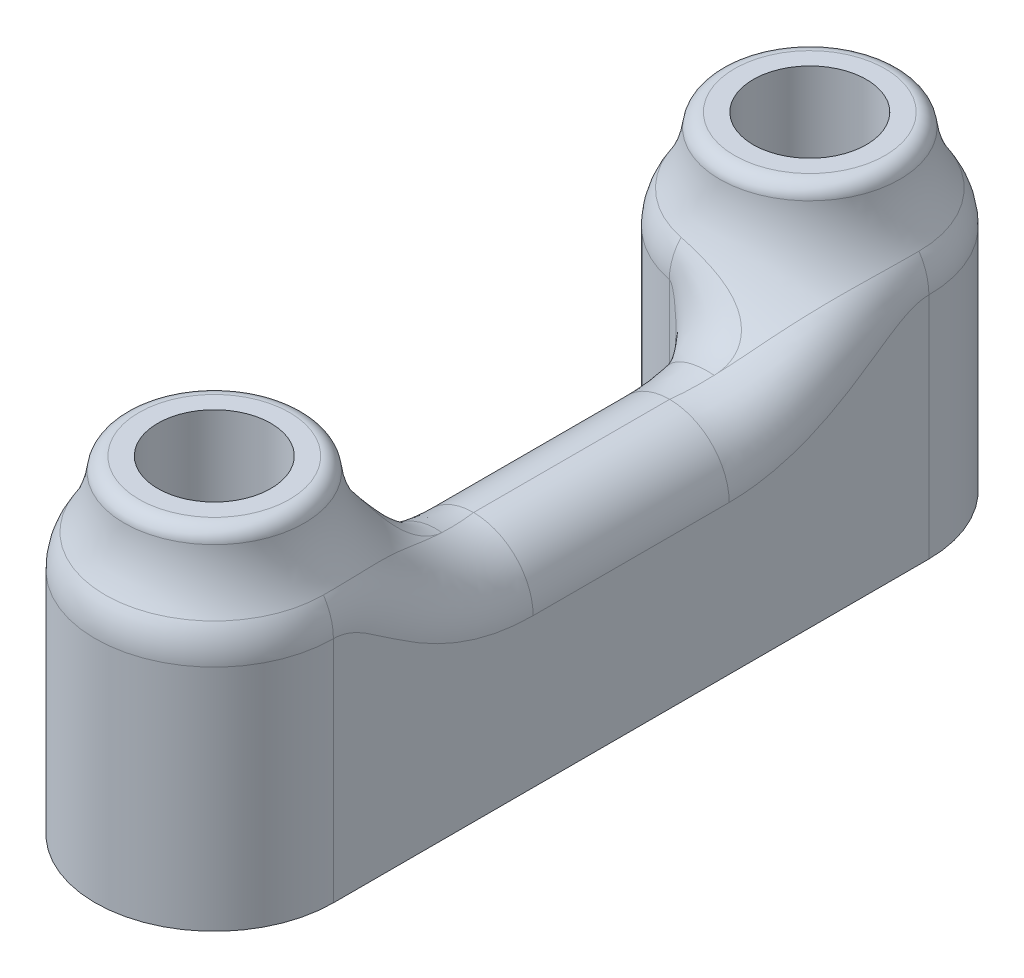
SolidWorks part; units mm, degrees
ref_plane "Front Plane" through (0, 0, 0) normal (0, 0, 1) x (1, 0, 0)
ref_plane "Top Plane" through (0, 0, 0) normal (0, 1, 0) x (1, 0, 0)
ref_plane "Right Plane" through (0, 0, 0) normal (1, 0, 0) x (0, 0, -1)
sketch "Sketch1" plane through (0, 0, 0) normal (0, 1, 0) x (1, 0, 0)
  line L0 (0, 7.62) -> (0, -7.62)
  line L1 (5.08, 12.7) -> (5.08, -12.7)
  line L2 (5.08, 0) -> (0, 0) construction
  arc A0 (5.08, 12.7) -> (0, 7.62) centre (0, 12.7) ccw
  circle A1 centre (0, 12.7) radius 2.413
  circle A2 centre (0, -12.7) radius 2.413
  arc A3 (5.08, -12.7) -> (0, -7.62) centre (0, -12.7) cw
  dimension "D1" = 4.826
  dimension "D2" = 10.16
  dimension "D3" = 12.7
extrude "Boss-Extrude1" add sketch "Sketch1" along normal blind 8.89
sketch "Sketch2" plane through (0, 8.89, 0) normal (0, 1, 0) x (1, 0, 0)
  line L0 (0, 0) -> (5.08, 0) construction
  line L1 (0, 7.62) -> (0, -7.62) construction
  line L2 (5.08, -12.7) -> (5.08, 12.7) construction
  circle A0 centre (0, 12.7) radius 2.413
  circle A1 centre (0, 12.7) radius 3.81
  circle A2 centre (0, 12.7) radius 2.413 construction
  circle A3 centre (0, -12.7) radius 3.81
  circle A4 centre (0, -12.7) radius 2.413
  dimension "D1" = 7.62
extrude "Boss-Extrude2" add sketch "Sketch2" along normal blind 5.08
fillet "Fillet1" radius 5.08 2 edges at (0, 8.89, 8.89) (0, 8.89, -8.89)
fillet "Fillet2" radius 1.27 2 edges at (0, 5.3049, -7.62) (0, 5.3049, 7.62)
fillet "Fillet3" radius 2.54 10 edges at (0, 9.083, -5.1968) (-0.494, 10.4371, -7.4837) (-3.2129, 10.6099, -16.635) (5.08, 10.3708, -11.1712) (5.08, 8.89, 0) (5.08, 9.41, 8.407) (-3.2129, 10.6099, 16.635) (-0.4001, 10.3644, 7.4036) (0, 9.083, 5.1968) (0, 8.89, 0)
fillet "Fillet4" radius 0.635 2 edges at (0, 13.97, 8.89) (0, 13.97, -8.89)
